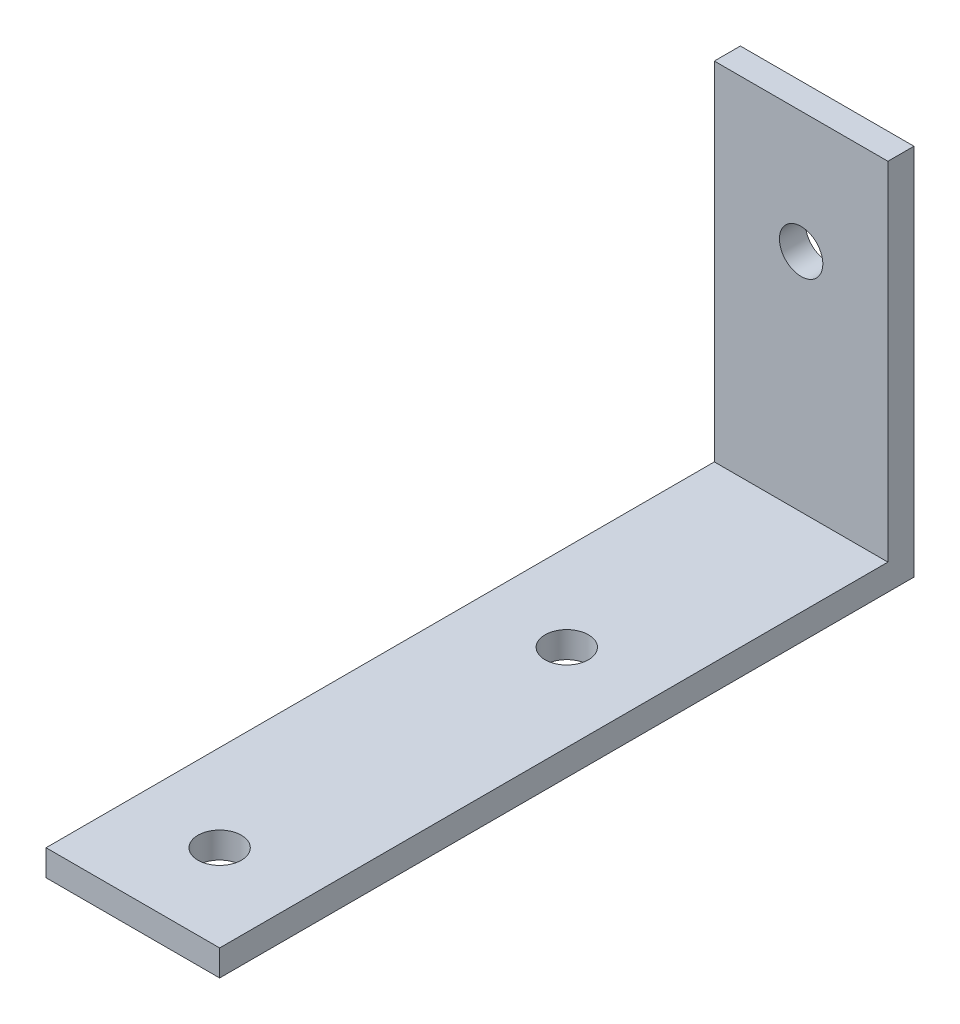
SolidWorks part; units mm, degrees
material "ABS"
ref_plane "Front Plane" through (0, 0, 0) normal (0, 0, 1) x (1, 0, 0)
ref_plane "Top Plane" through (0, 0, 0) normal (0, 1, 0) x (1, 0, 0)
ref_plane "Right Plane" through (0, 0, 0) normal (1, 0, 0) x (0, 0, -1)
sketch "Sketch1" plane through (0, 0, 0) normal (0, 1, 0) x (1, 0, 0)
  line L0 (0, 40) -> (0, -40) construction
  line L1 (-10, 40) -> (10, 40)
  line L2 (-10, 40) -> (-10, -40)
  line L3 (-10, -40) -> (10, -40)
  line L4 (10, 40) -> (10, -40)
  line L5 (-10, 40) -> (10, -40) construction
  line L6 (-10, -40) -> (10, 40) construction
  circle A1 centre (0, -30) radius 2.5
  circle A2 centre (0, 10) radius 2.5
  point P0 (0, 0)
  point P8 (0, -30.4782)
  point P9 (0, 9.784)
  point P14 (0, 0)
  point P15 (0, 12.7506)
extrude "Boss-Extrude1" add sketch "Sketch1" along normal blind 3
sketch "Sketch2" plane through (0, 3, 0) normal (0, 1, 0) x (1, 0, 0)
  line L0 (10, -40) -> (10, 40) construction
  line L1 (-10, 40) -> (10, 40)
  line L2 (-10, 40) -> (-10, 37)
  line L3 (-10, 37) -> (10, 37)
  line L4 (10, 40) -> (10, 37)
extrude "Boss-Extrude2" add sketch "Sketch2" along normal blind 40
sketch "Sketch3" plane through (0, 0, -40) normal (0, 0, -1) x (-1, 0, 0)
  line L0 (0, 0) -> (0, 43) construction
  line L1 (-10, 43) -> (10, 43) construction
  circle A0 centre (0, 29) radius 2.5
extrude "Cut-Extrude1" cut sketch "Sketch3" against normal blind 3
